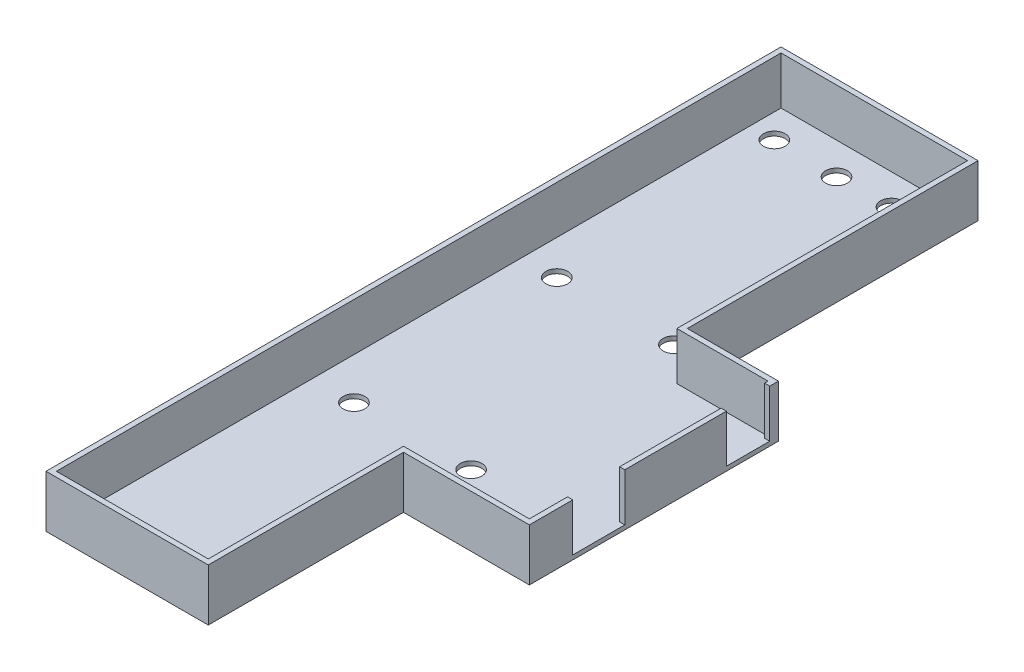
SolidWorks part; units mm, degrees
note: The reader was unsure of these and kept them because the rebuilt part matched: shared geometry of "Sketch1<3>".
ref_plane "Front Plane" through (0, 0, 0) normal (0, 0, 1) x (1, 0, 0)
ref_plane "Top Plane" through (0, 0, 0) normal (0, 1, 0) x (1, 0, 0)
ref_plane "Right Plane" through (0, 0, 0) normal (1, 0, 0) x (0, 0, -1)
sketch "Sketch1" plane through (0, 0, 0) normal (0, 1, 0) x (1, 0, 0)
  line L0 (0, 0) -> (0, -167)
  line L1 (0, 0) -> (43, 0)
  line L2 (43, 0) -> (43, -67)
  line L3 (43, -67) -> (64, -67)
  line L4 (64, -67) -> (64, -122)
  line L5 (64, -122) -> (35, -122)
  line L6 (35, -122) -> (35, -167)
  line L7 (0, -167) -> (35, -167)
  line L8 (-1.2, 1.2) -> (-1.2, -168.2)
  line L9 (-1.2, -168.2) -> (36.2, -168.2)
  line L10 (36.2, -123.2) -> (36.2, -168.2)
  line L11 (65.2, -123.2) -> (36.2, -123.2)
  line L12 (65.2, -65.8) -> (65.2, -123.2)
  line L13 (44.2, -65.8) -> (65.2, -65.8)
  line L14 (44.2, 1.2) -> (44.2, -65.8)
  line L15 (-1.2, 1.2) -> (44.2, 1.2)
  dimension "D1" = 167
  dimension "D2" = 43
  dimension "D3" = 67
  dimension "D4" = 21
  dimension "D5" = 55
  dimension "D6" = 29
  dimension "D7" = 1.2
extrude "Boss-Extrude1" add sketch "Sketch1" along normal blind 1 contours L0 L7 L6 L5 L4 L3 L2 L1 | L15 L8 L9 L10 L11 L12 L13 L14 L7 L0 L1 L2 L3 L4 L5 L6
extrude "Boss-Extrude2" add sketch "Sketch1<3>" along normal blind 12 contours L9 L10 L11 L12 L13 L14 L15 L8
sketch "Sketch1<3>" plane through (0, 0, 0) normal (0, 1, 0) x (1, 0, 0) same geometry as "Sketch1"
sketch "Sketch2" plane through (65.2, 0, 0) normal (1, 0, 0) x (0, 0, -1)
  line L0 (-123.2, 12) -> (-65.8, 12) construction
  line L1 (-77.8, 12) -> (-67.8, 12)
  line L2 (-77.8, 12) -> (-77.8, 1)
  line L3 (-77.8, 1) -> (-67.8, 1)
  line L4 (-67.8, 12) -> (-67.8, 1)
  line L5 (-65.8, 12) -> (-65.8, 0) construction
  line L6 (-67, 0) -> (-122, 0) construction
  line L7 (-123.2, 12) -> (-123.2, 0) construction
  line L8 (-113.2, 12) -> (-101.2, 12)
  line L9 (-113.2, 12) -> (-113.2, 1)
  line L10 (-113.2, 1) -> (-101.2, 1)
  line L11 (-101.2, 12) -> (-101.2, 1)
  point P10 (-72.8, 1)
  dimension "D1" = 2
  dimension "D2" = 10
  dimension "D3" = 1
  dimension "D4" = 10
  dimension "D5" = 12
extrude "Cut-Extrude1" cut sketch "Sketch2" against normal blind 12
sketch "Sketch3" plane through (0, 1, 0) normal (0, 1, 0) x (1, 0, 0)
  circle A0 centre (5.5926, -7.1409) radius 2.5
  circle A1 centre (20.1395, -7.3502) radius 2.5
  circle A2 centre (32.4886, -7.0362) radius 2.5
  circle A3 centre (7.9997, -59.677) radius 2.5
  circle A4 centre (34.8957, -59.5724) radius 2.5
  circle A5 centre (9.5794, -108.0037) radius 2.5
  circle A6 centre (36.4754, -107.899) radius 2.5
  circle A7 centre (4.5115, -160.2798) radius 2.5
  circle A8 centre (31.4075, -160.1751) radius 2.5
  dimension "D1" = 5
extrude "Cut-Extrude2" cut sketch "Sketch3" against normal blind 12
